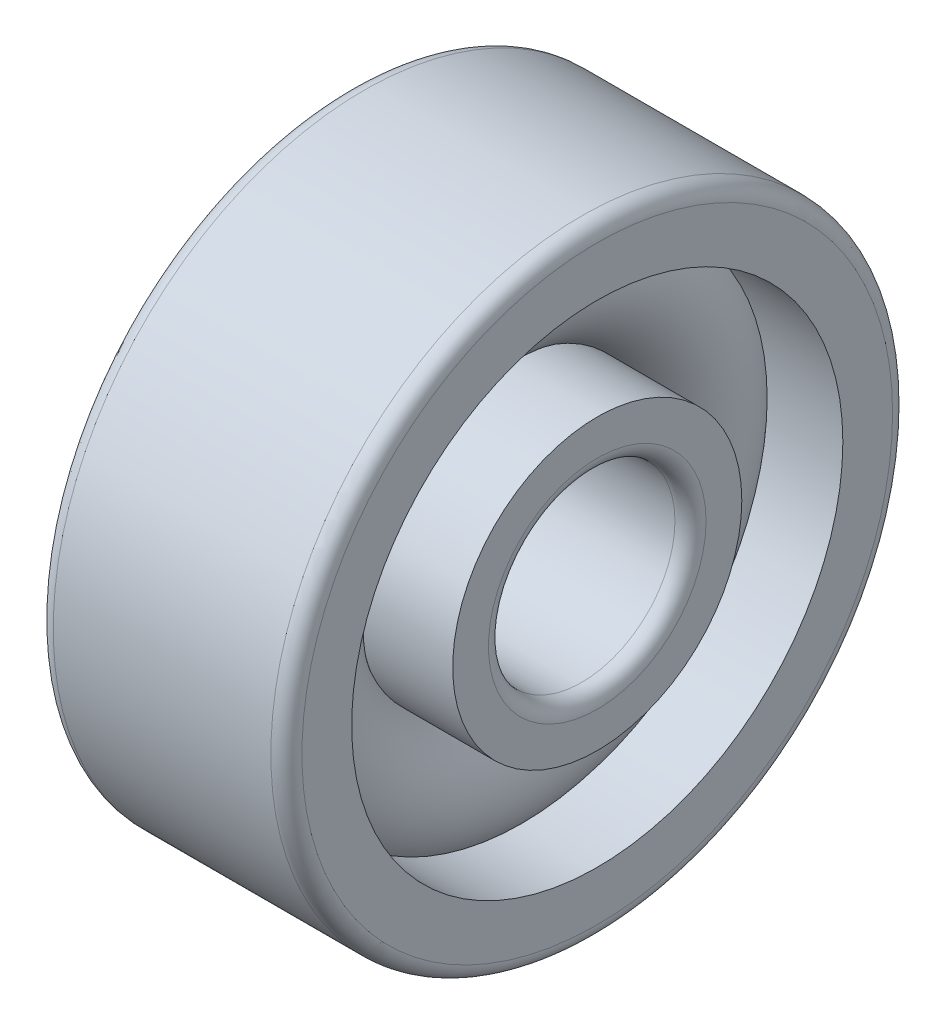
SolidWorks part; units mm, degrees
ref_plane "Plane1" through (0, 0, 0) normal (0, 0, 1) x (1, 0, 0)
ref_plane "Plane2" through (0, 0, 0) normal (0, 1, 0) x (1, 0, 0)
ref_plane "Plane3" through (0, 0, 0) normal (1, 0, 0) x (0, 0, -1)
sketch "Clipboard" plane through (0, 0, 0) normal (0, 0, 1) x (1, 0, 0)
  line L0 (-10, 0) -> (10, 0) construction
  line L1 (0, 0) -> (22.3471, -0.7804)
  line L2 (0, 0) -> (0.6496, 0.0227)
  line L3 (0, 0) -> (22.3471, -0.7804)
  line L4 (0, 0) -> (-22.3573, -0.3902)
sketch "CagSpiSke" plane through (0, 0, 0) normal (0, 0, 1) x (1, 0, 0)
  line L0 (0.0525, 0.615) -> (0.0525, 0.685)
  line L1 (0.0525, 0.685) -> (-0.0525, 0.685)
  line L2 (-0.0525, 0.685) -> (-0.0525, 0.615)
  line L3 (-0.0525, 0.615) -> (0.0525, 0.615)
  line L4 (-20.6375, 0) -> (20.6375, 0) construction
  line L5 (0, 0) -> (0, 23.7692) construction
revolve "CageSpine" add sketch "CagSpiSke" angle 0.001 about L4
ref_axis "Axis1" through (-50, 0, 0) along (1, 0, 0)
sketch "CagBalSke" plane through (0, 0, 0) normal (0, 0, 1) x (1, 0, 0)
  line L0 (-0.231, 0.65) -> (0.231, 0.65)
  line L1 (-1.905, 0.65) -> (1.905, 0.65) construction
  line L2 (-10, 0) -> (10, 0) construction
  line L3 (0, 0) -> (0, 24) construction
  arc A0 (0.231, 0.65) -> (-0.231, 0.65) centre (0, 0.65) cw
revolve "CageBall" [suppressed] add sketch "CagBalSke" angle 360 about L1 reverse direction yes
pattern_circular "CageBalls" [suppressed] count 2 every 180 about axis through (-50, 0, 0) along (1, 0, 0)
sketch "CagTrmODSke" plane through (0, 0, 0) normal (0, 0, 1) x (1, 0, 0)
  line L0 (0.232, 0.685) -> (0.232, 0.882)
  line L1 (0.232, 0.882) -> (-0.232, 0.882)
  line L2 (-0.232, 0.882) -> (-0.232, 0.685)
  line L3 (-0.232, 0.685) -> (0.232, 0.685)
  line L4 (-20.6375, 0) -> (20.6375, 0) construction
  line L5 (0, 0) -> (0, 25) construction
revolve "CageTrimOD" [suppressed] cut sketch "CagTrmODSke" angle 360 about L4 reverse direction yes
sketch "CagTrmIDSke" plane through (0, 0, 0) normal (0, 0, 1) x (1, 0, 0)
  line L0 (0.232, 0.42) -> (0.232, 0.615)
  line L1 (0.232, 0.615) -> (-0.232, 0.615)
  line L2 (-0.232, 0.615) -> (-0.232, 0.42)
  line L3 (-0.232, 0.42) -> (0.232, 0.42)
  line L4 (-20.6375, 0) -> (20.6375, 0) construction
  line L5 (0, 0) -> (0, 25) construction
revolve "CageTrimID" [suppressed] cut sketch "CagTrmIDSke" angle 360 about L4 reverse direction yes
sketch "BalSimSke" plane through (0, 0, 0) normal (0, 0, 1) x (1, 0, 0)
  line L0 (-10, 0) -> (10, 0) construction
  line L1 (-10, 0.65) -> (10, 0.65) construction
  line L2 (0, 0) -> (0, 23) construction
  circle A0 centre (0, 0.65) radius 0.21
revolve "BallsSimplified" add sketch "BalSimSke" angle 360 about L0
sketch "BalDetSke" plane through (0, 0, 0) normal (0, 0, 1) x (1, 0, 0)
  line L0 (-0.21, 0.65) -> (0.21, 0.65)
  line L1 (-1.905, 0.65) -> (1.905, 0.65) construction
  line L2 (0, 0) -> (0, 25) construction
  arc A0 (0.21, 0.65) -> (-0.21, 0.65) centre (0, 0.65) cw
revolve "BallDetailed" [suppressed] add sketch "BalDetSke" angle 360 about L1 reverse direction yes
sketch "InnRacSke" plane through (0, 0, 0) normal (0, 0, 1) x (1, 0, 0)
  line L0 (-0.1209, 0.51) -> (-0.4, 0.51)
  line L1 (-0.4, 0.51) -> (-0.4, 0.35)
  line L2 (-0.35, 0.3) -> (0.35, 0.3)
  line L3 (0.4, 0.35) -> (0.4, 0.465)
  line L4 (0, 0.465) -> (0.4, 0.465)
  line L5 (-20.6375, 0) -> (20.6375, 0) construction
  line L6 (0, 0) -> (0, 30) construction
  arc A0 (-0.4, 0.35) -> (-0.35, 0.3) centre (-0.35, 0.35) ccw
  arc A1 (0.35, 0.3) -> (0.4, 0.35) centre (0.35, 0.35) ccw
  arc A2 (0, 0.465) -> (-0.1209, 0.51) centre (0, 0.65) cw
revolve "InnerRace" add sketch "InnRacSke" angle 360 about L5 reverse direction yes
sketch "OutRacSke" plane through (0, 0, 0) normal (0, 0, 1) x (1, 0, 0)
  line L0 (0, 0.835) -> (-0.4, 0.835)
  line L1 (-0.4, 0.835) -> (-0.4, 0.95)
  line L2 (-0.35, 1) -> (0.35, 1)
  line L3 (0.4, 0.95) -> (0.4, 0.79)
  line L4 (0.4, 0.79) -> (0.1209, 0.79)
  line L5 (-20.6375, 0) -> (20.6375, 0) construction
  line L6 (0, 0) -> (0, 30) construction
  arc A0 (-0.4, 0.95) -> (-0.35, 1) centre (-0.35, 0.95) cw
  arc A1 (0.35, 1) -> (0.4, 0.95) centre (0.35, 0.95) cw
  arc A2 (0.1209, 0.79) -> (0, 0.835) centre (0, 0.65) ccw
revolve "OuterRace" add sketch "OutRacSke" angle 360 about L5 reverse direction yes
pattern_circular "BallsDetailed" [suppressed] count 2 every 180 about axis through (-50, 0, 0) along (1, 0, 0)
equation "\"BallCLRad@Clipboard\" = ( \"OD@OutRacSke\" + \"ID@InnRacSke\" ) / 4"
equation "\"BallCLRad@BalSimSke\" = \"BallCLRad@Clipboard\""
equation "\"BallCLRad@BalDetSke\" = \"BallCLRad@Clipboard\""
equation "\"BallCLRad@InnRacSke\" = \"BallCLRad@Clipboard\""
equation "\"BallCLRad@OutRacSke\" = \"BallCLRad@Clipboard\""
equation "\"Ball_diameter@InnRacSke\" = \"Ball_diameter@BalDetSke\" - 0.05"
equation "\"Ball_diameter@OutRacSke\" = \"Ball_diameter@BalDetSke\" - 0.05"
equation "\"Ball_diameter@BalSimSke\" = \"Ball_diameter@BalDetSke\""
equation "\"Width@OutRacSke\" = \"Width@InnRacSke\""
equation "\"Fillet_radius@OutRacSke\" = \"Fillet_radius@InnRacSke\""
equation "\"Max_count@Clipboard\" = int( 3.14159265 / atn(( \"Ball_diameter@BalDetSke\" / 2) / sqr( \"BallCLRad@Clipboard\"  *  \"BallCLRad@Clipboard\" - ( \"Ball_diameter@BalDetSke\" / 2) *  ( \"Ball_diameter@BalDetSke\" / 2))))"
equation "\"Max_count@Clipboard\" = ((sgn( \"Max_count@Clipboard\" - \"Count@Clipboard\" )-1)*( \"Max_count@Clipboard\" - \"Count@Clipboard\" ))/-2+ \"Count@Clipboard\""
equation "\"Count@BallsDetailed\" = int( \"Show_count@Clipboard\" ) "
equation "\"Count@BallsDetailed\" = ((sgn( \"Count@BallsDetailed\" - \"Max_count@Clipboard\" )-1)*( \"Count@BallsDetailed\" - \"Max_count@Clipboard\" ))/-2+ \"Max_count@Clipboard\""
equation "\"Count@BallsDetailed\" = ((sgn( \"Count@BallsDetailed\" - \"Min_count@Clipboard\" )+1)*( \"Count@BallsDetailed\" - \"Min_count@Clipboard\"))/2 +\"Min_count@Clipboard\""
equation "\"Angle@BallsDetailed\" = 360.0 / \"Max_count@Clipboard\""
equation "\"BallCLRad@CagBalSke\" = \"BallCLRad@Clipboard\""
equation "\"Count@CageBalls\" = \"Count@BallsDetailed\""
equation "\"Angle@CageBalls\" = \"Angle@BallsDetailed\""
equation "\"Angle@CageSpine\" =  \"Angle@CageBalls\" * ( \"Count@CageBalls\" -1 + int( \"Count@CageBalls\" / \"Max_count@Clipboard\" ) )  + 0.001 -  int( \"Count@CageBalls\" / \"Max_count@Clipboard\" ) * 0.001"
equation "\"Angle@CageSpine\" =  \"Angle@CageSpine\" * int( \"Min_count@Clipboard\" / 2) + int(1 / \"Min_count@Clipboard\")  * 0.001"
equation "\"CageWallOD@CagBalSke\" =  \"Ball_diameter@BalDetSke\" * 1.1"
equation "\"Thickness@CagSpiSke\" =  \"Ball_diameter@BalDetSke\" * 0.25"
equation "\"OD@CagTrmODSke\" = \"BallCLRad@Clipboard\" * 2 + \"CageWallOD@CagBalSke\" + 0.002"
equation "\"ID@CagTrmODSke\" = \"BallCLRad@Clipboard\" * 2 + \"Ball_diameter@BalDetSke\" / 6"
equation "\"OD@CagTrmIDSke\" = \"BallCLRad@Clipboard\" * 2 - \"Ball_diameter@BalDetSke\" / 6"
equation "\"ID@CagTrmIDSke\" = \"BallCLRad@Clipboard\" * 2 - \"CageWallOD@CagBalSke\" + 0.002"
equation "\"OD@CagSpiSke\" = \"ID@CagTrmODSke\""
equation "\"ID@CagSpiSke\" = \"OD@CagTrmIDSke\""
equation "\"Width@CagTrmODSke\" = \"CageWallOD@CagBalSke\" + 0.002"
equation "\"Width@CagTrmIDSke\" = \"CageWallOD@CagBalSke\" + 0.002"
